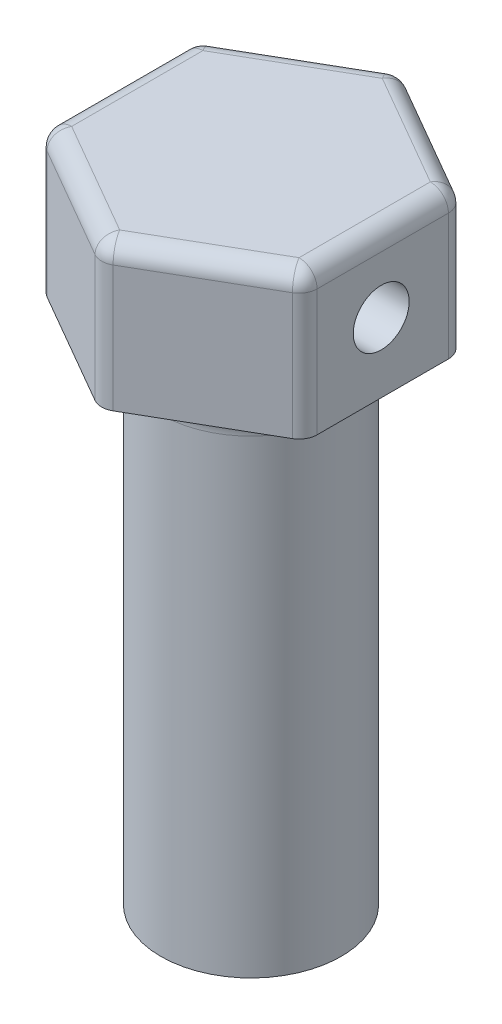
SolidWorks part; units mm, degrees
ref_plane "Front Plane" through (0, 0, 0) normal (0, 0, 1) x (1, 0, 0)
ref_plane "Top Plane" through (0, 0, 0) normal (0, 1, 0) x (1, 0, 0)
ref_plane "Right Plane" through (0, 0, 0) normal (1, 0, 0) x (0, 0, -1)
sketch "Sketch1" plane through (0, 0, 0) normal (0, 1, 0) x (1, 0, 0)
  line L1 (7.3, -4.2147) -> (7.3, 4.2147)
  line L2 (7.3, 4.2147) -> (0, 8.4293)
  line L3 (0, 8.4293) -> (-7.3, 4.2147)
  line L4 (-7.3, 4.2147) -> (-7.3, -4.2147)
  line L5 (-7.3, -4.2147) -> (0, -8.4293)
  line L6 (0, -8.4293) -> (7.3, -4.2147)
  circle A0 centre (0, 0) radius 7.3 construction
  dimension "D1" = 14.6
extrude "Boss-Extrude1" add sketch "Sketch1" along normal blind 8
sketch "Sketch2" plane through (0, 0, 0) normal (0, -1, 0) x (1, 0, 0)
  line L0 (-1.15, 1.0392) -> (-1.15, -1.0392)
  line L1 (-7.3, -4.2147) -> (-7.3, 4.2147) construction
  arc A0 (-1.15, -1.0392) -> (-1.15, 1.0392) centre (0, 0) ccw
  circle A1 centre (0, 0) radius 5
  dimension "D1" = 3.1
  dimension "D2" = 10
  dimension "D3" = 1.15
extrude "Boss-Extrude2" add sketch "Sketch2" along normal blind 28 contours A1 | A0 L0
fillet "Fillet1" radius 2 1 edges at (0, 0, 5)
sketch "Sketch3" plane through (7.3, 0, 0) normal (1, 0, 0) x (0, 0, -1)
  line L0 (-7, 0) -> (7, 0) construction
  line L1 (4.2147, 8) -> (4.2147, 0) construction
  circle A0 centre (-0.0853, 3.85) radius 1.55
  dimension "D1" = 3.1
  dimension "D2" = 3.85
  dimension "D3" = 4.3
extrude "Cut-Extrude1" cut sketch "Sketch3" against normal through all
fillet "Fillet2" radius 1 12 edges at (-3.65, 8, 6.322) (-7.3, 8, 0) (-3.65, 8, -6.322) (3.65, 8, -6.322) (7.3, 8, 0) (3.65, 8, 6.322) (-7.3, 4, -4.2147) (0, 4, -8.4293) (7.3, 4, -4.2147) (7.3, 4, 4.2147) (0, 4, 8.4293) (-7.3, 4, 4.2147)
sketch "Sketch4" plane through (0, 0, 0) normal (1, 0, 0) x (0, 0, -1)
  line L1 (-16.1086, 1.5942) -> (18.1695, 1.5942)
  line L2 (-16.1086, 1.5942) -> (-16.1086, -34.824)
  line L3 (-16.1086, -34.824) -> (18.1695, -34.824)
  line L4 (18.1695, 1.5942) -> (18.1695, -34.824)
extrude "Cut-Extrude2" [suppressed] cut sketch "Sketch4" against normal through all both and the other way through all
sketch "Sketch5" plane through (0, -28, 0) normal (0, -1, 0) x (1, 0, 0)
  circle A0 centre (0, 0) radius 1.55
  dimension "D1" = 3.1
extrude "Cut-Extrude3" cut sketch "Sketch5" against normal blind 4
equation "\"1.ø15\"=1.5"
